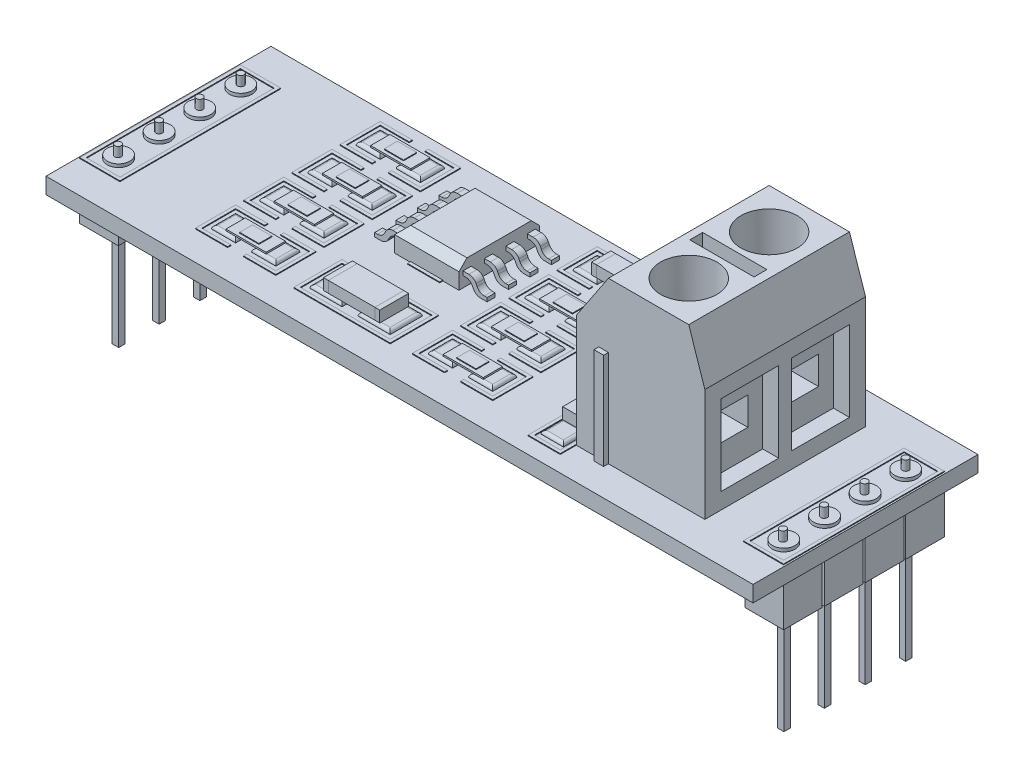
SolidWorks part; units mm, degrees
ref_plane "Front" through (0, 0, 0) normal (0, 0, 1) x (1, 0, 0)
ref_plane "Top" through (0, 0, 0) normal (0, 1, 0) x (1, 0, 0)
ref_plane "Right" through (0, 0, 0) normal (1, 0, 0) x (0, 0, -1)
sketch "Sketch1" plane through (0, 0, 0) normal (0, 1, 0) x (1, 0, 0)
  line L1 (-22, -7) -> (22, -7)
  line L2 (-22, -7) -> (-22, 7)
  line L3 (-22, 7) -> (22, 7)
  line L4 (22, -7) -> (22, 7)
  line L5 (-22, -7) -> (22, 7) construction
  line L6 (-22, 7) -> (22, -7) construction
  point P0 (0, 0)
  dimension "D1" = 44
  dimension "D2" = 14
extrude "Boss-Extrude1" add sketch "Sketch1" along normal blind 1
sketch "Sketch2" plane through (0, 0, 0) normal (0, -1, 0) x (1, 0, 0)
  line L0 (19.5, -2.6) -> (19.5, -5)
  line L1 (19.5, -5) -> (21.9, -5)
  line L2 (21.9, -5) -> (21.9, -2.6)
  line L3 (21.9, -2.6) -> (19.5, -2.6)
  line L4 (19.5, -0.08) -> (19.5, -2.48)
  line L5 (19.5, -2.48) -> (21.9, -2.48)
  line L6 (21.9, -2.48) -> (21.9, -0.08)
  line L7 (21.9, -0.08) -> (19.5, -0.08)
  line L8 (19.5, 2.46) -> (19.5, 0.06)
  line L9 (19.5, 0.06) -> (21.9, 0.06)
  line L10 (21.9, 0.06) -> (21.9, 2.46)
  line L11 (21.9, 2.46) -> (19.5, 2.46)
  line L12 (19.5, 5) -> (19.5, 2.6)
  line L13 (19.5, 2.6) -> (21.9, 2.6)
  line L14 (21.9, 2.6) -> (21.9, 5)
  line L15 (21.9, 5) -> (19.5, 5)
  line L16 (-21.9, 2.6) -> (-19.5, 2.6)
  line L17 (-19.5, 2.6) -> (-19.5, 5)
  line L18 (-19.5, 5) -> (-21.9, 5)
  line L19 (-21.9, 5) -> (-21.9, 2.6)
  line L20 (-21.9, 0.06) -> (-19.5, 0.06)
  line L21 (-19.5, 0.06) -> (-19.5, 2.46)
  line L22 (-19.5, 2.46) -> (-21.9, 2.46)
  line L23 (-21.9, 2.46) -> (-21.9, 0.06)
  line L24 (-21.9, -2.48) -> (-19.5, -2.48)
  line L25 (-19.5, -2.48) -> (-19.5, -0.08)
  line L26 (-19.5, -0.08) -> (-21.9, -0.08)
  line L27 (-21.9, -0.08) -> (-21.9, -2.48)
  line L28 (-21.9, -5) -> (-19.5, -5)
  line L29 (-19.5, -5) -> (-19.5, -2.6)
  line L30 (-19.5, -2.6) -> (-21.9, -2.6)
  line L31 (-21.9, -2.6) -> (-21.9, -5)
extrude "Boss-Extrude2" add sketch "Sketch2" along normal blind 2.5
sketch "Sketch3" plane through (0, -2.5, 0) normal (0, -1, 0) x (1, 0, 0)
  line L0 (-20.5, -1.08) -> (-20.9, -1.08)
  line L3 (-20.9, -1.08) -> (-20.9, -1.48)
  line L6 (-20.5, -4) -> (-20.5, -3.6)
  line L7 (-20.5, -3.6) -> (-20.9, -3.6)
  line L8 (-20.9, -3.6) -> (-20.9, -4)
  line L9 (-20.9, -4) -> (-20.5, -4)
  line L10 (-20.5, -1.48) -> (-20.5, -1.08)
  line L11 (-20.9, -1.48) -> (-20.5, -1.48)
  line L12 (-20.9, 3.98) -> (-20.9, 3.58)
  line L13 (-20.5, 3.58) -> (-20.5, 3.98)
  line L14 (-20.5, 1.46) -> (-20.9, 1.46)
  line L15 (-20.5, 1.06) -> (-20.5, 1.46)
  line L16 (-20.9, 3.58) -> (-20.5, 3.58)
  line L17 (-20.9, 1.46) -> (-20.9, 1.06)
  line L18 (-20.9, 1.06) -> (-20.5, 1.06)
  line L19 (-20.5, 3.98) -> (-20.9, 3.98)
  line L20 (20.9, -4) -> (20.9, -3.6)
  line L21 (20.5, 1.46) -> (20.5, 1.06)
  line L22 (20.5, -1.48) -> (20.9, -1.48)
  line L23 (20.9, -1.08) -> (20.5, -1.08)
  line L24 (20.5, -4) -> (20.9, -4)
  line L25 (20.5, 1.06) -> (20.9, 1.06)
  line L26 (20.5, 3.58) -> (20.9, 3.58)
  line L27 (20.9, -3.6) -> (20.5, -3.6)
  line L28 (20.5, -1.08) -> (20.5, -1.48)
  line L29 (20.9, 3.58) -> (20.9, 3.98)
  line L30 (20.9, 1.06) -> (20.9, 1.46)
  line L31 (20.9, -1.48) -> (20.9, -1.08)
  line L32 (20.5, 3.98) -> (20.5, 3.58)
  line L33 (20.9, 1.46) -> (20.5, 1.46)
  line L34 (20.9, 3.98) -> (20.5, 3.98)
  line L35 (20.5, -3.6) -> (20.5, -4)
extrude "Boss-Extrude3" add sketch "Sketch3" along normal blind 6.5
sketch "Sketch4" plane through (0, 1, 0) normal (0, 1, 0) x (1, 0, 0)
  line L0 (21.9, 5) -> (19.4, 5)
  line L1 (19.4, 5) -> (19.4, -5)
  line L2 (19.4, -5) -> (21.9, -5)
  line L3 (21.9, -5) -> (21.9, 5)
  line L4 (9, -1) -> (7, -1)
  line L5 (7, -1) -> (7, -6)
  line L6 (7, -6) -> (9, -6)
  line L7 (9, -6) -> (9, -1)
  line L8 (9, 5.5) -> (7, 5.5)
  line L9 (7, 5.5) -> (7, 3.5)
  line L10 (7, 3.5) -> (7.2, 3.5)
  line L11 (7.2, 3.5) -> (7.2, 5.3)
  line L12 (7.2, 5.3) -> (8.8, 5.3)
  line L13 (8.8, 5.3) -> (8.8, 0.7)
  line L14 (8.8, 0.7) -> (7.2, 0.7)
  line L15 (7.2, 0.7) -> (7.2, 2.5)
  line L16 (7.2, 2.5) -> (7, 2.5)
  line L17 (7, 2.5) -> (7, 0.5)
  line L18 (7, 0.5) -> (9, 0.5)
  line L19 (9, 0.5) -> (9, 5.5)
  line L20 (4, -5.2) -> (4, -2.7)
  line L21 (4, -2.7) -> (2, -2.7)
  line L22 (2, -2.7) -> (2, -2.9)
  line L23 (2, -2.9) -> (3.8, -2.9)
  line L24 (3.8, -2.9) -> (3.8, -5)
  line L25 (3.8, -5) -> (2, -5)
  line L26 (2, -5) -> (2, -5.2)
  line L27 (2, -5.2) -> (4, -5.2)
  line L28 (4, -2.2) -> (4, 0.3)
  line L29 (4, 0.3) -> (2, 0.3)
  line L30 (2, 0.3) -> (2, 0.1)
  line L31 (2, 0.1) -> (3.8, 0.1)
  line L32 (3.8, 0.1) -> (3.8, -2)
  line L33 (3.8, -2) -> (2, -2)
  line L34 (2, -2) -> (2, -2.2)
  line L35 (2, -2.2) -> (4, -2.2)
  line L36 (2, 0.8) -> (4, 0.8)
  line L37 (4, 0.8) -> (4, 3.3)
  line L38 (4, 3.3) -> (2, 3.3)
  line L39 (2, 3.3) -> (2, 3.1)
  line L40 (2, 3.1) -> (3.8, 3.1)
  line L41 (3.8, 3.1) -> (3.8, 1)
  line L42 (3.8, 1) -> (2, 1)
  line L43 (2, 1) -> (2, 0.8)
  line L44 (4, 3.8) -> (4, 6.3)
  line L45 (4, 6.3) -> (2, 6.3)
  line L46 (2, 6.3) -> (2, 6.1)
  line L47 (2, 6.1) -> (3.8, 6.1)
  line L48 (3.8, 6.1) -> (3.8, 4)
  line L49 (3.8, 4) -> (2, 4)
  line L50 (2, 4) -> (2, 3.8)
  line L51 (2, 3.8) -> (4, 3.8)
  line L52 (-1, 3.8) -> (1, 3.8)
  line L53 (1, 3.8) -> (1, 4)
  line L54 (1, 4) -> (-0.8, 4)
  line L55 (-0.8, 4) -> (-0.8, 6.1)
  line L56 (-0.8, 6.1) -> (1, 6.1)
  line L57 (1, 6.1) -> (1, 6.3)
  line L58 (1, 6.3) -> (-1, 6.3)
  line L59 (-1, 6.3) -> (-1, 3.8)
  line L60 (1, 1) -> (-0.8, 1)
  line L61 (-0.8, 1) -> (-0.8, 3.1)
  line L62 (-0.8, 3.1) -> (1, 3.1)
  line L63 (1, 3.1) -> (1, 3.3)
  line L64 (1, 3.3) -> (-1, 3.3)
  line L65 (-1, 3.3) -> (-1, 0.8)
  line L66 (-1, 0.8) -> (1, 0.8)
  line L67 (1, 0.8) -> (1, 1)
  line L68 (-1, 0.3) -> (-1, -2.2)
  line L69 (-1, -2.2) -> (1, -2.2)
  line L70 (1, -2.2) -> (1, -2)
  line L71 (1, -2) -> (-0.8, -2)
  line L72 (-0.8, -2) -> (-0.8, 0.1)
  line L73 (-0.8, 0.1) -> (1, 0.1)
  line L74 (1, 0.1) -> (1, 0.3)
  line L75 (1, 0.3) -> (-1, 0.3)
  line L76 (1, -2.7) -> (-1, -2.7)
  line L77 (-1, -2.7) -> (-1, -5.2)
  line L78 (-1, -5.2) -> (1, -5.2)
  line L79 (1, -5.2) -> (1, -5)
  line L80 (1, -5) -> (-0.8, -5)
  line L81 (-0.8, -5) -> (-0.8, -2.9)
  line L82 (-0.8, -2.9) -> (1, -2.9)
  line L83 (1, -2.9) -> (1, -2.7)
  line L84 (-2.25, -2.3309) -> (-8.25, -2.3309)
  line L85 (-8.25, -2.3309) -> (-8.25, -5.3309)
  line L86 (-8.25, -5.3309) -> (-2.25, -5.3309)
  line L87 (-2.25, -5.3309) -> (-2.25, -2.3309)
  line L88 (-9.5, 3.8) -> (-9.5, 6.3)
  line L89 (-9.5, 6.3) -> (-11.5, 6.3)
  line L90 (-11.5, 6.3) -> (-11.5, 6.1)
  line L91 (-11.5, 6.1) -> (-9.7, 6.1)
  line L92 (-9.7, 6.1) -> (-9.7, 4)
  line L93 (-9.7, 4) -> (-11.5, 4)
  line L94 (-11.5, 4) -> (-11.5, 3.8)
  line L95 (-11.5, 3.8) -> (-9.5, 3.8)
  line L96 (-9.5, 0.8) -> (-9.5, 3.3)
  line L97 (-9.5, 3.3) -> (-11.5, 3.3)
  line L98 (-11.5, 3.3) -> (-11.5, 3.1)
  line L99 (-11.5, 3.1) -> (-9.7, 3.1)
  line L100 (-9.7, 3.1) -> (-9.7, 1)
  line L101 (-9.7, 1) -> (-11.5, 1)
  line L102 (-11.5, 1) -> (-11.5, 0.8)
  line L103 (-11.5, 0.8) -> (-9.5, 0.8)
  line L104 (-9.5, -2.2) -> (-9.5, 0.3)
  line L105 (-9.5, 0.3) -> (-11.5, 0.3)
  line L106 (-11.5, 0.3) -> (-11.5, 0.1)
  line L107 (-11.5, 0.1) -> (-9.7, 0.1)
  line L108 (-9.7, 0.1) -> (-9.7, -2)
  line L109 (-9.7, -2) -> (-11.5, -2)
  line L110 (-11.5, -2) -> (-11.5, -2.2)
  line L111 (-11.5, -2.2) -> (-9.5, -2.2)
  line L112 (-9.5, -5.2) -> (-9.5, -2.7)
  line L113 (-9.5, -2.7) -> (-11.5, -2.7)
  line L114 (-11.5, -2.7) -> (-11.5, -2.9)
  line L115 (-11.5, -2.9) -> (-9.7, -2.9)
  line L116 (-9.7, -2.9) -> (-9.7, -5)
  line L117 (-9.7, -5) -> (-11.5, -5)
  line L118 (-11.5, -5) -> (-11.5, -5.2)
  line L119 (-11.5, -5.2) -> (-9.5, -5.2)
  line L120 (-14.5, -2.7) -> (-14.5, -5.2)
  line L121 (-14.5, -5.2) -> (-12.5, -5.2)
  line L122 (-12.5, -5.2) -> (-12.5, -5)
  line L123 (-12.5, -5) -> (-14.3, -5)
  line L124 (-14.3, -5) -> (-14.3, -2.9)
  line L125 (-14.3, -2.9) -> (-12.5, -2.9)
  line L126 (-12.5, -2.9) -> (-12.5, -2.7)
  line L127 (-12.5, -2.7) -> (-14.5, -2.7)
  line L128 (-14.5, 0.3) -> (-14.5, -2.2)
  line L129 (-14.5, -2.2) -> (-12.5, -2.2)
  line L130 (-12.5, -2.2) -> (-12.5, -2)
  line L131 (-12.5, -2) -> (-14.3, -2)
  line L132 (-14.3, -2) -> (-14.3, 0.1)
  line L133 (-14.3, 0.1) -> (-12.5, 0.1)
  line L134 (-12.5, 0.1) -> (-12.5, 0.3)
  line L135 (-12.5, 0.3) -> (-14.5, 0.3)
  line L136 (-14.5, 3.3) -> (-14.5, 0.8)
  line L137 (-14.5, 0.8) -> (-12.5, 0.8)
  line L138 (-12.5, 0.8) -> (-12.5, 1)
  line L139 (-12.5, 1) -> (-14.3, 1)
  line L140 (-14.3, 1) -> (-14.3, 3.1)
  line L141 (-14.3, 3.1) -> (-12.5, 3.1)
  line L142 (-12.5, 3.1) -> (-12.5, 3.3)
  line L143 (-12.5, 3.3) -> (-14.5, 3.3)
  line L144 (-14.5, 6.3) -> (-14.5, 3.8)
  line L145 (-14.5, 3.8) -> (-12.5, 3.8)
  line L146 (-12.5, 3.8) -> (-12.5, 4)
  line L147 (-12.5, 4) -> (-14.3, 4)
  line L148 (-14.3, 4) -> (-14.3, 6.1)
  line L149 (-14.3, 6.1) -> (-12.5, 6.1)
  line L150 (-12.5, 6.1) -> (-12.5, 6.3)
  line L151 (-12.5, 6.3) -> (-14.5, 6.3)
  line L152 (-19.4, 5) -> (-21.9, 5)
  line L153 (-21.9, 5) -> (-21.9, -5)
  line L154 (-21.9, -5) -> (-19.4, -5)
  line L155 (-19.4, -5) -> (-19.4, 5)
  line L156 (-4.2, -0.3) -> (-5.8, -0.3)
  line L157 (8.8, -5.8) -> (7.2, -5.8)
  line L158 (7.2, -5.8) -> (7.2, -1.2)
  line L159 (8.8, -1.2) -> (8.8, -5.8)
  line L160 (7.2, -1.2) -> (8.8, -1.2)
  line L161 (-19.6, -4.8) -> (-21.7, -4.8)
  line L162 (-21.7, -4.8) -> (-21.7, 4.8)
  line L163 (-19.6, 4.8) -> (-19.6, -4.8)
  line L164 (-21.7, 4.8) -> (-19.6, 4.8)
  line L165 (19.6, 4.8) -> (21.7, 4.8)
  line L166 (21.7, 4.8) -> (21.7, -4.8)
  line L167 (21.7, -4.8) -> (19.6, -4.8)
  line L168 (19.6, -4.8) -> (19.6, 4.8)
  line L169 (-8.05, -5.1309) -> (-8.05, -2.5309)
  line L170 (-8.05, -2.5309) -> (-2.45, -2.5309)
  line L171 (-2.45, -5.1309) -> (-8.05, -5.1309)
  line L172 (-2.45, -2.5309) -> (-2.45, -5.1309)
  line L173 (-5.8, 4.8) -> (-5.8, -0.3)
  line L174 (-4, 5) -> (-6, 5)
  line L175 (-6, 5) -> (-6, -0.5)
  line L176 (-6, -0.5) -> (-4, -0.5)
  line L177 (-4, -0.5) -> (-4, 5)
  line L178 (-4.2, 4.8) -> (-5.8, 4.8)
  line L179 (-4.2, 4.8) -> (-4.2, -0.3)
extrude "Boss-Extrude4" add sketch "Sketch4" along normal blind 0.05
sketch "Sketch6" plane through (0, 1, 0) normal (0, 1, 0) x (1, 0, 0)
  circle A0 centre (-20.7, -1.26) radius 0.7
  circle A1 centre (-20.7, 1.2632) radius 0.7
  circle A2 centre (-20.7, 3.8198) radius 0.7
  circle A3 centre (20.7123, -3.8) radius 0.7
  circle A4 centre (20.7123, -1.26) radius 0.7
  circle A5 centre (20.7123, 1.2632) radius 0.7
  circle A6 centre (-20.7, -3.7832) radius 0.7
  circle A7 centre (20.7123, 3.7864) radius 0.7
extrude "Boss-Extrude5" add sketch "Sketch6" along normal blind 0.2
sketch "Sketch8" plane through (0, 1.2, 0) normal (0, 1, 0) x (1, 0, 0)
  circle A0 centre (-20.7, 3.8198) radius 0.2
  circle A1 centre (-20.7, 1.2632) radius 0.2
  circle A2 centre (-20.7, -3.8166) radius 0.2
  circle A3 centre (-20.7, -1.26) radius 0.2
  circle A4 centre (20.7123, 1.2298) radius 0.2
  circle A5 centre (20.7123, -1.2934) radius 0.2
  circle A6 centre (20.7123, 3.7864) radius 0.2
  circle A7 centre (20.7123, -3.85) radius 0.2
  dimension "D1" = 0.4
  dimension "D2" = 0.4
extrude "Boss-Extrude6" add sketch "Sketch8" along normal blind 0.6
sketch "Sketch9" plane through (0, 1, 0) normal (0, 1, 0) x (1, 0, 0)
  line L4 (-3, -0.3) -> (-7, -0.3)
  line L5 (-3, -0.3) -> (-3, 4.7)
  line L6 (-3, 4.7) -> (-7, 4.7)
  line L7 (-7, -0.3) -> (-7, 4.7)
extrude "Boss-Extrude7" add sketch "Sketch9" along normal blind 1.5
chamfer "Chamfer1" distance 0.5 angle 45 3 edges at (-5, 2.5, -4.7) (-5, 2.5, 0.3) (-7, 2.5, -2.2)
sketch "Sketch10" plane through (0, 0, 0.3) normal (0, 0, 1) x (1, 0, 0)
  line L0 (-22, 1) -> (22, 1) construction
  line L1 (-22, 1) -> (22, 1) construction
  line L2 (-7, 2) -> (-7, 1) construction
  line L3 (-7, 2) -> (-7, 1) construction
  line L4 (-1.9012, 1) -> (-1.5, 1)
  line L5 (-1.5, 1) -> (-1.5, 1.2358)
  line L6 (-1.5, 1.2358) -> (-1.6739, 1.2358)
  line L7 (-2.1229, 1.5158) -> (-2.1843, 1.6412)
  line L8 (-2.6333, 1.9213) -> (-3, 1.9213)
  line L9 (-3, 1.9213) -> (-3, 1.6699)
  line L10 (-3, 1.6699) -> (-2.853, 1.6699)
  line L11 (-2.4039, 1.3898) -> (-2.3502, 1.2801)
  line L12 (-8.3261, 1.2358) -> (-8.5, 1.2358)
  line L13 (-8.5, 1.2358) -> (-8.5, 1)
  line L14 (-8.5, 1) -> (-8.0988, 1)
  line L15 (-7.6498, 1.2801) -> (-7.5961, 1.3898)
  line L16 (-7.147, 1.6699) -> (-7, 1.6699)
  line L17 (-7, 1.6699) -> (-7, 1.9213)
  line L18 (-7, 1.9213) -> (-7.3667, 1.9213)
  line L19 (-7.8157, 1.6412) -> (-7.8771, 1.5158)
  arc A0 (-2.3502, 1.2801) -> (-1.9012, 1) centre (-1.9012, 1.5) ccw
  arc A1 (-2.1229, 1.5158) -> (-1.6739, 1.2358) centre (-1.6739, 1.7358) ccw
  arc A2 (-2.1843, 1.6412) -> (-2.6333, 1.9213) centre (-2.6333, 1.4213) ccw
  arc A3 (-2.4039, 1.3898) -> (-2.853, 1.6699) centre (-2.853, 1.1699) ccw
  arc A4 (-8.0988, 1) -> (-7.6498, 1.2801) centre (-8.0988, 1.5) ccw
  arc A5 (-7.147, 1.6699) -> (-7.5961, 1.3898) centre (-7.147, 1.1699) ccw
  arc A6 (-7.3667, 1.9213) -> (-7.8157, 1.6412) centre (-7.3667, 1.4213) ccw
  arc A7 (-8.3261, 1.2358) -> (-7.8771, 1.5158) centre (-8.3261, 1.7358) ccw
extrude "Boss-Extrude8" add sketch "Sketch10" against normal blind 0.5 from offset 0.25 offset against normal yes
pattern_linear "LPattern1" count 4 spacing 1.3333 along (0, 0, -1) of "Boss-Extrude8"
sketch "Sketch11" plane through (0, 1, 0) normal (0, 1, 0) x (1, 0, 0)
  line L1 (-12.5, 5.8) -> (-12.5, 4.3)
  line L2 (-14, 4.3) -> (-14, 5.8)
  line L3 (-11.5, 4.3) -> (-11.5, 5.8)
  line L4 (-10, 5.8) -> (-10, 4.3)
  line L5 (-14, 5.8) -> (-12.5, 5.8)
  line L6 (-14, 4.3) -> (-12.5, 4.3)
  line L7 (-11.5, 4.3) -> (-10, 4.3)
  line L8 (-11.5, 5.8) -> (-10, 5.8)
  line L10 (3.5, 5.8) -> (3.5, 4.3)
  line L11 (2, 4.3) -> (3.5, 4.3)
  line L12 (1, 5.8) -> (1, 4.3)
  line L13 (-0.5, 4.3) -> (-0.5, 5.8)
  line L14 (2, 4.3) -> (2, 5.8)
  line L15 (-0.5, 4.3) -> (1, 4.3)
  line L16 (-0.5, 5.8) -> (1, 5.8)
  line L17 (2, 5.8) -> (3.5, 5.8)
extrude "Boss-Extrude9" add sketch "Sketch11" along normal blind 0.2
fillet "Fillet1" radius 0.19 16 edges at (2.75, 1.2, -4.3) (2, 1.2, -5.05) (3.5, 1.2, -5.05) (2.75, 1.2, -5.8) (0.25, 1.2, -4.3) (1, 1.2, -5.05) (0.25, 1.2, -5.8) (-0.5, 1.2, -5.05) (-10, 1.2, -5.05) (-10.75, 1.2, -5.8) (-10.75, 1.2, -4.3) (-11.5, 1.2, -5.05) (-13.25, 1.2, -5.8) (-12.5, 1.2, -5.05) (-13.25, 1.2, -4.3) (-14, 1.2, -5.05)
pattern_linear "LPattern2" count 4 spacing 3 along (0, 0, 1) of "Fillet1", "Boss-Extrude9"
sketch "Sketch12" plane through (0, 1.2, 0) normal (0, 1, 0) x (1, 0, 0)
  line L0 (0.2609, -4.55) -> (2.7609, -4.55)
  line L1 (2.7609, -4.55) -> (2.7609, -3.35)
  line L2 (2.7609, -3.35) -> (0.2609, -3.35)
  line L3 (0.2609, -3.35) -> (0.2609, -4.55)
  line L4 (0.2609, -1.55) -> (2.7609, -1.55)
  line L5 (2.7609, -1.55) -> (2.7609, -0.35)
  line L6 (2.7609, -0.35) -> (0.2609, -0.35)
  line L7 (0.2609, -0.35) -> (0.2609, -1.55)
  line L8 (0.2609, 1.45) -> (2.7609, 1.45)
  line L9 (2.7609, 1.45) -> (2.7609, 2.65)
  line L10 (2.7609, 2.65) -> (0.2609, 2.65)
  line L11 (0.2609, 2.65) -> (0.2609, 1.45)
  line L12 (-13.25, -4.55) -> (-10.75, -4.55)
  line L13 (-10.75, -4.55) -> (-10.75, -3.35)
  line L14 (-10.75, -3.35) -> (-13.25, -3.35)
  line L15 (-13.25, -3.35) -> (-13.25, -4.55)
  line L16 (-13.25, -1.55) -> (-10.75, -1.55)
  line L17 (-10.75, -1.55) -> (-10.75, -0.35)
  line L18 (-10.75, -0.35) -> (-13.25, -0.35)
  line L19 (-13.25, -0.35) -> (-13.25, -1.55)
  line L20 (-13.25, 1.45) -> (-10.75, 1.45)
  line L21 (-10.75, 1.45) -> (-10.75, 2.65)
  line L22 (-10.75, 2.65) -> (-13.25, 2.65)
  line L23 (-13.25, 2.65) -> (-13.25, 1.45)
  line L24 (-13.25, 4.45) -> (-10.75, 4.45)
  line L25 (-10.75, 4.45) -> (-10.75, 5.65)
  line L26 (-10.75, 5.65) -> (-13.25, 5.65)
  line L27 (-13.25, 5.65) -> (-13.25, 4.45)
extrude "Boss-Extrude10" add sketch "Sketch12" along normal blind 0.1
sketch "Sketch13" plane through (0, 1.3, 0) normal (0, 1, 0) x (1, 0, 0)
  line L0 (0.9109, -4.35) -> (2.1109, -4.35)
  line L1 (2.1109, -4.35) -> (2.1109, -3.55)
  line L2 (2.1109, -3.55) -> (0.9109, -3.55)
  line L3 (0.9109, -3.55) -> (0.9109, -4.35)
  line L4 (0.9109, -1.35) -> (2.1109, -1.35)
  line L5 (2.1109, -1.35) -> (2.1109, -0.5152)
  line L6 (2.1109, -0.5152) -> (0.9109, -0.5152)
  line L7 (0.9109, -0.5152) -> (0.9109, -1.35)
  line L8 (0.9109, 1.65) -> (2.1109, 1.65)
  line L9 (2.1109, 1.65) -> (2.1109, 2.4914)
  line L10 (2.1109, 2.4914) -> (0.9109, 2.4914)
  line L11 (0.9109, 2.4914) -> (0.9109, 1.65)
  line L12 (-12.6, -4.35) -> (-11.4, -4.35)
  line L13 (-11.4, -4.35) -> (-11.4, -3.55)
  line L14 (-11.4, -3.55) -> (-12.6, -3.55)
  line L15 (-12.6, -3.55) -> (-12.6, -4.35)
  line L16 (-12.6, -1.35) -> (-11.4, -1.35)
  line L17 (-11.4, -1.35) -> (-11.4, -0.5152)
  line L18 (-11.4, -0.5152) -> (-12.6, -0.5152)
  line L19 (-12.6, -0.5152) -> (-12.6, -1.35)
  line L20 (-12.6, 1.65) -> (-11.4, 1.65)
  line L21 (-11.4, 1.65) -> (-11.4, 2.4914)
  line L22 (-11.4, 2.4914) -> (-12.6, 2.4914)
  line L23 (-12.6, 2.4914) -> (-12.6, 1.65)
  line L24 (-11.4, 5.4671) -> (-12.6, 5.4671)
  line L25 (-12.6, 5.4671) -> (-12.6, 4.65)
  line L26 (-12.6, 4.65) -> (-11.4, 4.65)
  line L27 (-11.4, 4.65) -> (-11.4, 5.4671)
extrude "Boss-Extrude11" add sketch "Sketch13" along normal blind 0.05
sketch "Sketch15" plane through (0, 1, 0) normal (0, 1, 0) x (1, 0, 0)
  line L0 (-4.75, -4.8309) -> (-4.75, -2.8309)
  line L1 (-2.75, -4.8309) -> (-4.75, -4.8309)
  line L2 (-5.75, -4.8309) -> (-7.75, -4.8309)
  line L3 (-2.75, -2.8309) -> (-2.75, -4.8309)
  line L4 (-4.75, -2.8309) -> (-2.75, -2.8309)
  line L5 (-7.75, -2.8309) -> (-5.75, -2.8309)
  line L6 (-5.75, -2.8309) -> (-5.75, -4.8309)
  line L7 (-7.75, -4.8309) -> (-7.75, -2.8309)
  line L8 (8.7, -5.5) -> (7.3, -5.5)
  line L9 (7.3, -5.5) -> (7.3, -4.1)
  line L11 (7.3, -2.9) -> (8.7, -2.9)
  line L12 (8.7, 1) -> (7.3, 1)
  line L13 (7.3, 1) -> (7.3, 2.4)
  line L14 (8.7, 3.6) -> (7.3, 3.6)
  line L15 (7.3, 3.6) -> (7.3, 5)
  line L16 (7.3, 5) -> (8.7, 5)
  line L17 (8.7, 3.6) -> (8.7, 5)
  line L18 (7.3, 2.4) -> (8.7, 2.4)
  line L19 (8.7, 1) -> (8.7, 2.4)
  line L20 (7.3, -4.1) -> (8.7, -4.1)
  line L21 (7.3, -2.9) -> (7.3, -1.5)
  line L22 (8.7, -5.5) -> (8.7, -4.1)
  line L23 (7.3, -1.5) -> (8.7, -1.5)
  line L27 (8.7, -2.9) -> (8.7, -1.5)
extrude "Boss-Extrude12" add sketch "Sketch15" along normal up to surface (0.2 mm away) up to face at (2.75, 1.2, -5.05)
fillet "Fillet2" radius 0.19 24 edges at (8, 1.2, 5.5) (7.3, 1.2, 4.8) (8, 1.2, 2.9) (7.3, 1.2, 2.2) (8, 1.2, -1) (7.3, 1.2, -1.7) (8, 1.2, 4.1) (8.7, 1.2, 4.8) (8.7, 1.2, 2.2) (8, 1.2, 1.5) (8, 1.2, -2.4) (8.7, 1.2, -1.7) (8.7, 1.2, -4.3) (8, 1.2, -5) (8, 1.2, -3.6) (7.3, 1.2, -4.3) (-2.75, 1.2, 3.8309) (-3.75, 1.2, 2.8309) (-5.75, 1.2, 3.8309) (-6.75, 1.2, 2.8309) (-7.75, 1.2, 3.8309) (-6.75, 1.2, 4.8309) (-3.75, 1.2, 4.8309) (-4.75, 1.2, 3.8309)
sketch "Sketch16" plane through (0, 1.2, 0) normal (0, 1, 0) x (1, 0, 0)
  line L1 (8.55, 4.25) -> (7.45, 4.25)
  line L2 (7.45, 4.25) -> (7.45, 1.75)
  line L3 (7.45, 1.75) -> (8.55, 1.75)
  line L4 (8.55, 1.75) -> (8.55, 4.25)
extrude "Boss-Extrude13" add sketch "Sketch16" along normal blind 0.1
sketch "Sketch17" plane through (0, 1.3, 0) normal (0, 1, 0) x (1, 0, 0)
  line L1 (8.35, 3.6) -> (7.65, 3.6)
  line L2 (7.65, 3.6) -> (7.65, 2.4)
  line L3 (7.65, 2.4) -> (8.35, 2.4)
  line L4 (8.35, 2.4) -> (8.35, 3.6)
extrude "Boss-Extrude14" add sketch "Sketch17" along normal blind 0.05
sketch "Sketch18" plane through (0, 1.2, 0) normal (0, 1, 0) x (1, 0, 0)
  line L1 (8.6, -2.7443) -> (7.4, -2.7443)
  line L2 (7.4, -2.7443) -> (7.4, -4.2443)
  line L3 (7.4, -4.2443) -> (8.6, -4.2443)
  line L4 (8.6, -4.2443) -> (8.6, -2.7443)
extrude "Boss-Extrude15" add sketch "Sketch18" along normal blind 0.7 separate body
sketch "Sketch19" plane through (0, 1.2, 0) normal (0, 1, 0) x (1, 0, 0)
  line L1 (-3.8, -4.7309) -> (-3.8, -2.9309)
  line L2 (-3.8, -2.9309) -> (-6.7, -2.9309)
  line L3 (-6.7, -2.9309) -> (-6.7, -4.7309)
  line L4 (-6.7, -4.7309) -> (-3.8, -4.7309)
extrude "Boss-Extrude16" add sketch "Sketch19" along normal blind 0.7
sketch "Sketch21" plane through (-6.7, 0, 0) normal (-1, 0, 0) x (0, 0, 1)
  line L6 (2.9309, 1.2) -> (3.0209, 1.2)
  line L7 (3.0209, 1.2) -> (4.6409, 1.2)
  line L8 (4.6409, 1.2) -> (4.7309, 1.2)
  line L9 (4.7309, 1.2) -> (4.7309, 1.9)
  line L10 (4.7309, 1.9) -> (2.9309, 1.9)
  line L11 (2.9309, 1.9) -> (2.9309, 1.2)
  line L12 (2.9309, 1.2) -> (3.0209, 1.2)
  line L13 (3.0209, 1.2) -> (4.6409, 1.2)
  line L14 (4.6409, 1.2) -> (4.7309, 1.2)
  line L15 (4.7309, 1.2) -> (4.7309, 1.9)
  line L16 (4.7309, 1.9) -> (2.9309, 1.9)
  line L17 (2.9309, 1.9) -> (2.9309, 1.2)
  dimension "D1" = 0
extrude "Boss-Extrude17" add sketch "Sketch21" along normal blind 0.3 separate body
sketch "Sketch22" plane through (-3.8, 0, 0) normal (1, 0, 0) x (0, 0, -1)
  line L6 (-4.7309, 1.2) -> (-4.6409, 1.2)
  line L7 (-4.6409, 1.2) -> (-3.0209, 1.2)
  line L8 (-3.0209, 1.2) -> (-2.9309, 1.2)
  line L9 (-2.9309, 1.2) -> (-2.9309, 1.9)
  line L10 (-2.9309, 1.9) -> (-4.7309, 1.9)
  line L11 (-4.7309, 1.9) -> (-4.7309, 1.2)
  line L12 (-4.7309, 1.2) -> (-4.6409, 1.2)
  line L13 (-4.6409, 1.2) -> (-3.0209, 1.2)
  line L14 (-3.0209, 1.2) -> (-2.9309, 1.2)
  line L15 (-2.9309, 1.2) -> (-2.9309, 1.9)
  line L16 (-2.9309, 1.9) -> (-4.7309, 1.9)
  line L17 (-4.7309, 1.9) -> (-4.7309, 1.2)
  dimension "D1" = 0
extrude "Boss-Extrude18" add sketch "Sketch22" along normal blind 0.3 separate body
sketch "Sketch23" plane through (0, 1.2, 0) normal (0, 1, 0) x (1, 0, 0)
  line L1 (2.2, 4.45) -> (2.2, 5.65)
  line L2 (2.2, 5.65) -> (0.8, 5.65)
  line L3 (0.8, 5.65) -> (0.8, 4.45)
  line L4 (0.8, 4.45) -> (2.2, 4.45)
extrude "Boss-Extrude19" add sketch "Sketch23" along normal blind 0.7
sketch "Sketch24" plane through (0.8, 0, 0) normal (-1, 0, 0) x (0, 0, 1)
  line L6 (-5.65, 1.2) -> (-5.61, 1.2)
  line L7 (-5.61, 1.2) -> (-4.49, 1.2)
  line L8 (-4.49, 1.2) -> (-4.45, 1.2)
  line L9 (-4.45, 1.2) -> (-4.45, 1.9)
  line L10 (-4.45, 1.9) -> (-5.65, 1.9)
  line L11 (-5.65, 1.9) -> (-5.65, 1.2)
  line L12 (-5.65, 1.2) -> (-5.61, 1.2)
  line L13 (-5.61, 1.2) -> (-4.49, 1.2)
  line L14 (-4.49, 1.2) -> (-4.45, 1.2)
  line L15 (-4.45, 1.2) -> (-4.45, 1.9)
  line L16 (-4.45, 1.9) -> (-5.65, 1.9)
  line L17 (-5.65, 1.9) -> (-5.65, 1.2)
  dimension "D1" = 0
extrude "Boss-Extrude20" add sketch "Sketch24" along normal blind 0.3 separate body
sketch "Sketch25" plane through (2.2, 0, 0) normal (1, 0, 0) x (0, 0, -1)
  line L6 (4.45, 1.2) -> (4.49, 1.2)
  line L7 (4.49, 1.2) -> (5.61, 1.2)
  line L8 (5.61, 1.2) -> (5.65, 1.2)
  line L9 (5.65, 1.2) -> (5.65, 1.9)
  line L10 (5.65, 1.9) -> (4.45, 1.9)
  line L11 (4.45, 1.9) -> (4.45, 1.2)
  line L12 (4.45, 1.2) -> (4.49, 1.2)
  line L13 (4.49, 1.2) -> (5.61, 1.2)
  line L14 (5.61, 1.2) -> (5.65, 1.2)
  line L15 (5.65, 1.2) -> (5.65, 1.9)
  line L16 (5.65, 1.9) -> (4.45, 1.9)
  line L17 (4.45, 1.9) -> (4.45, 1.2)
  dimension "D1" = 0
extrude "Boss-Extrude21" add sketch "Sketch25" along normal blind 0.3 separate body
sketch "Sketch26" plane through (0, 0, 7) normal (0, 0, 1) x (1, 0, 0)
  line L0 (17, 1) -> (9, 1)
  line L1 (-22, 1) -> (22, 1) construction
  line L2 (17, 1) -> (17, 8)
  line L3 (17, 8) -> (16, 11)
  line L4 (16, 11) -> (11, 11)
  line L5 (11, 11) -> (9, 8)
  line L6 (9, 8) -> (9, 1)
extrude "Boss-Extrude22" add sketch "Sketch26" against normal blind 10 from offset 2 offset against normal yes
sketch "Sketch27" plane through (0, 11, 0) normal (0, 1, 0) x (1, 0, 0)
  line L0 (11.464, -0.4) -> (15.464, -0.4)
  line L1 (15.464, -0.4) -> (15.464, 0.4)
  line L2 (15.464, 0.4) -> (11.464, 0.4)
  line L3 (11.464, 0.4) -> (11.464, -0.4)
  line L4 (13.5, 5) -> (13.5, -5) construction
  line L5 (16, 5) -> (11, 5) construction
  line L6 (16, -5) -> (11, -5) construction
  circle A0 centre (13.5, 2.5) radius 1.75
  circle A1 centre (13.5, -2.5) radius 1.75
extrude "Cut-Extrude1" cut sketch "Sketch27" against normal blind 3
sketch "Sketch29" plane through (0, 0, 5) normal (0, 0, 1) x (1, 0, 0)
  line L1 (10.4, 7) -> (10.4, 1)
  line L2 (10.4, 1) -> (11, 1)
  line L3 (11, 1) -> (11, 7)
  line L4 (11, 7) -> (10.4, 7)
extrude "Boss-Extrude23" add sketch "Sketch29" along normal blind 0.3
sketch "Sketch30" plane through (0, 0, -5) normal (0, 0, -1) x (-1, 0, 0)
  line L4 (-10.4, 7) -> (-11, 7)
  line L5 (-10.4, 1) -> (-10.4, 7)
  line L6 (-11, 1) -> (-10.4, 1)
  line L7 (-11, 7) -> (-11, 1)
  line L8 (-10.4, 7) -> (-11, 7)
  line L9 (-10.4, 1) -> (-10.4, 7)
  line L10 (-11, 1) -> (-10.4, 1)
  line L11 (-11, 7) -> (-11, 1)
  dimension "D1" = 0
extrude "Cut-Extrude2" cut sketch "Sketch30" against normal blind 0.5
sketch "Sketch31" plane through (17, 0, 0) normal (1, 0, 0) x (0, 0, -1)
  line L0 (4, 7) -> (0.4, 7)
  line L1 (-4, 7) -> (-4, 2)
  line L2 (-4, 2) -> (-0.4, 2)
  line L3 (4, 2) -> (4, 7)
  line L4 (-5, 8) -> (-5, 1)
  line L5 (-5, 1) -> (5, 1)
  line L6 (5, 1) -> (5, 8)
  line L7 (5, 8) -> (-5, 8)
  line L8 (-5, 8) -> (-5, 1) construction
  line L9 (-5, 1) -> (5, 1) construction
  line L10 (5, 1) -> (5, 8) construction
  line L11 (5, 8) -> (-5, 8) construction
  line L12 (-0.4, 7) -> (-0.4, 2)
  line L13 (0.4, 7) -> (0.4, 2)
  line L14 (-0.4, 7) -> (-4, 7)
  line L15 (4, 7) -> (-4, 7) construction
  line L16 (0.4, 11) -> (-0.4, 11)
  line L17 (-0.4, 11) -> (-0.4, 8)
  line L18 (-0.4, 8) -> (0.4, 8)
  line L19 (0.4, 8) -> (0.4, 11)
  line L20 (0.4, 11) -> (-0.4, 11) construction
  line L21 (-0.4, 11) -> (-0.4, 8) construction
  line L22 (-0.4, 8) -> (0.4, 8) construction
  line L23 (0.4, 8) -> (0.4, 11) construction
  line L24 (0.4, 2) -> (4, 2)
  line L25 (-4, 2) -> (4, 2) construction
  line L29 (-3.075, 5.375) -> (-1.325, 5.375)
  line L30 (-3.075, 5.375) -> (-3.075, 3.625)
  line L31 (-3.075, 3.625) -> (-1.325, 3.625)
  line L32 (-1.325, 5.375) -> (-1.325, 3.625)
  line L33 (-3.075, 5.375) -> (-1.325, 3.625) construction
  line L34 (-3.075, 3.625) -> (-1.325, 5.375) construction
  line L35 (1.325, 5.375) -> (3.075, 5.375)
  line L36 (1.325, 5.375) -> (1.325, 3.625)
  line L37 (1.325, 3.625) -> (3.075, 3.625)
  line L38 (3.075, 5.375) -> (3.075, 3.625)
  line L39 (1.325, 5.375) -> (3.075, 3.625) construction
  line L40 (1.325, 3.625) -> (3.075, 5.375) construction
  point P20 (-2.2, 4.5)
  point P25 (2.2, 4.5)
  dimension "D4" = 1.75
  dimension "D5" = 1.75
  dimension "D6" = 1.75
  dimension "D7" = 1.75
  dimension "D1" = 0
  dimension "D2" = 1
  dimension "D3" = 0
extrude "Cut-Extrude3" cut sketch "Sketch31" against normal blind 1
sketch "Sketch32" plane through (17, 0, 0) normal (1, 0, 0) x (0, 0, -1)
  line L0 (1.325, 3.625) -> (3.075, 3.625) construction
  line L1 (3.075, 3.625) -> (3.075, 5.375) construction
  line L2 (3.075, 5.375) -> (1.325, 5.375) construction
  line L3 (1.325, 5.375) -> (1.325, 3.625) construction
  line L4 (-3.075, 3.625) -> (-1.325, 3.625) construction
  line L5 (-1.325, 3.625) -> (-1.325, 5.375) construction
  line L6 (-1.325, 5.375) -> (-3.075, 5.375) construction
  line L7 (-3.075, 5.375) -> (-3.075, 3.625) construction
  line L8 (1.325, 3.625) -> (3.075, 3.625)
  line L9 (3.075, 3.625) -> (3.075, 5.375)
  line L10 (3.075, 5.375) -> (1.325, 5.375)
  line L11 (1.325, 5.375) -> (1.325, 3.625)
  line L12 (-3.075, 3.625) -> (-1.325, 3.625)
  line L13 (-1.325, 3.625) -> (-1.325, 5.375)
  line L14 (-1.325, 5.375) -> (-3.075, 5.375)
  line L15 (-3.075, 5.375) -> (-3.075, 3.625)
extrude "Cut-Extrude4" cut sketch "Sketch32" against normal blind 3
sketch "Sketch33" plane through (0, 8, 0) normal (0, 1, 0) x (1, 0, 0)
  line L0 (11.7741, -2.7895) -> (15.2259, -2.7895)
  line L1 (11.7741, 2.7895) -> (15.2259, 2.7895)
  line L3 (11.7741, 2.2105) -> (15.2259, 2.2105)
  line L5 (11.7636, 2.7175) -> (15.2364, 2.2825) construction
  line L6 (11.7636, 2.2825) -> (15.2364, 2.7175) construction
  line L7 (11.7636, -2.2825) -> (15.2364, -2.7175) construction
  line L8 (11.7636, -2.7175) -> (15.2364, -2.2825) construction
  line L9 (11.7741, -2.2105) -> (15.2259, -2.2105)
  circle A0 centre (13.5, 2.5) radius 1.75 construction
  arc A1 (11.7741, 2.7895) -> (11.7741, 2.2105) centre (13.5, 2.5) ccw
  arc A2 (15.2259, 2.2105) -> (15.2259, 2.7895) centre (13.5, 2.5) ccw
  arc A3 (15.2259, -2.7895) -> (15.2259, -2.2105) centre (13.5, -2.5) ccw
  arc A4 (11.7741, -2.2105) -> (11.7741, -2.7895) centre (13.5, -2.5) ccw
  point P0 (13.5, 2.5)
  point P1 (13.5, -2.5)
extrude "Cut-Extrude5" cut sketch "Sketch33" against normal blind 1
